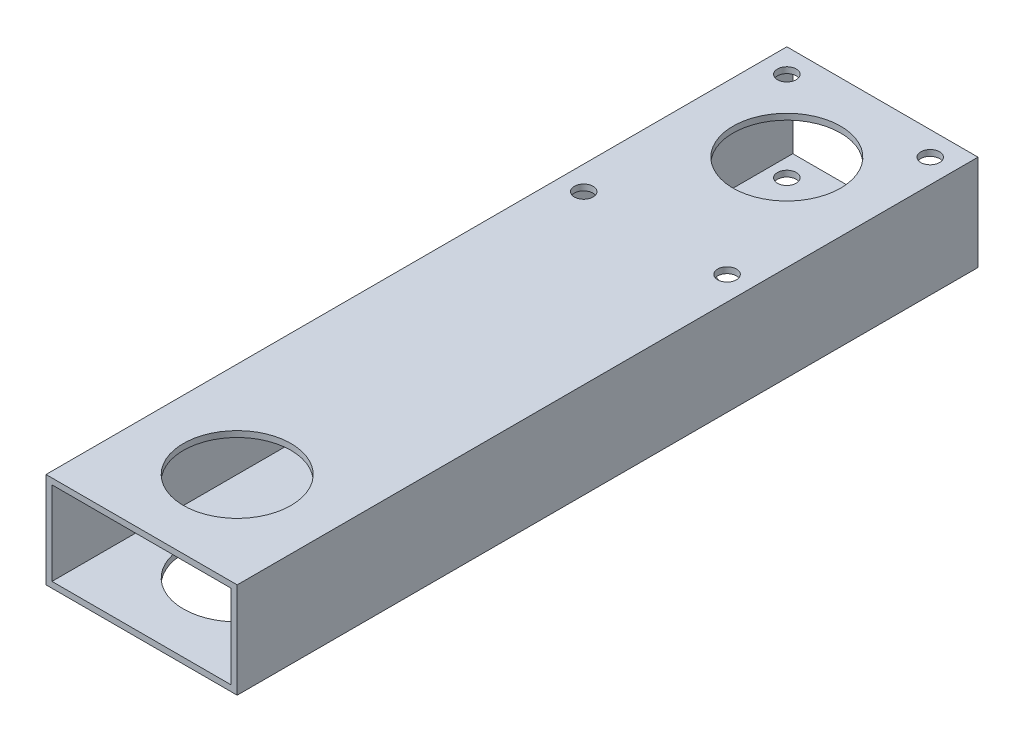
SolidWorks part; units mm, degrees
material "6061 Alloy"
ref_plane "Front Plane" through (0, 0, 0) normal (0, 0, 1) x (1, 0, 0)
ref_plane "Top Plane" through (0, 0, 0) normal (0, 1, 0) x (1, 0, 0)
ref_plane "Right Plane" through (0, 0, 0) normal (1, 0, 0) x (0, 0, -1)
sketch "Sketch1" plane through (0, 0, 0) normal (0, 0, 1) x (1, 0, 0)
  line L0 (-23.8125, 11.1125) -> (23.8125, 11.1125)
  line L2 (-25.4, 12.7) -> (25.4, 12.7)
  line L3 (-25.4, 12.7) -> (-25.4, -12.7)
  line L4 (-25.4, -12.7) -> (25.4, -12.7)
  line L5 (25.4, 12.7) -> (25.4, -12.7)
  line L10 (23.8125, 11.1125) -> (23.8125, -11.1125)
  line L11 (-23.8125, -11.1125) -> (23.8125, -11.1125)
  line L12 (-23.8125, 11.1125) -> (-23.8125, -11.1125)
  point P12 (0, 12.7)
  point P14 (25.4, 0)
  dimension "Wall Thickness" = 1.5875
  dimension "Outside Width" = 50.8
  dimension "Outside Height" = 25.4
  dimension "Inside Height" = 22.225
  dimension "Inside Width" = 47.625
sketch "Sketch2" plane through (0, 0, 0) normal (1, 0, 0) x (0, 0, -1)
  line L0 (98.425, 0) -> (-98.425, 0)
  point P4 (0, 0)
  point P7 (-98.425, 0)
  point P10 (98.425, 0)
  dimension "Length" = 196.85
sketch "Sketch3" plane through (0, 0, 0) normal (0, 0, 1) x (1, 0, 0)
  line L21 (25.4, 12.7) -> (-25.4, 12.7)
  line L22 (25.4, -12.7) -> (25.4, 12.7)
  line L23 (-25.4, -12.7) -> (25.4, -12.7)
  line L24 (-25.4, 12.7) -> (-25.4, -12.7)
  line L25 (25.4, 12.7) -> (-25.4, 12.7)
  line L26 (25.4, -12.7) -> (25.4, 12.7)
  line L27 (-25.4, -12.7) -> (25.4, -12.7)
  line L28 (-25.4, 12.7) -> (-25.4, -12.7)
  line L29 (23.8125, 11.1125) -> (-23.8125, 11.1125)
  line L30 (23.8125, -11.1125) -> (23.8125, 11.1125)
  line L31 (-23.8125, -11.1125) -> (23.8125, -11.1125)
  line L32 (-23.8125, 11.1125) -> (-23.8125, -11.1125)
  line L33 (23.8125, 11.1125) -> (-23.8125, 11.1125)
  line L34 (23.8125, -11.1125) -> (23.8125, 11.1125)
  line L35 (-23.8125, -11.1125) -> (23.8125, -11.1125)
  line L36 (-23.8125, 11.1125) -> (-23.8125, -11.1125)
  dimension "D1" = 0
  dimension "D2" = 0
extrude "Boss-Extrude1" add sketch "Sketch3" along normal up to vertex (98.425 mm away) and the other way up to vertex (98.425 mm away) up to point (0, 0, 98.425) other way up to point (0, 0, -98.425)
sketch "Drawing Reference" plane through (0, 0, 0) normal (1, 0, 0) x (0, 0, -1)
  line L0 (-98.425, 0) -> (98.425, 0) construction
  line L1 (0, -12.7) -> (0, 12.7) construction
  line L2 (-98.425, -12.7) -> (98.425, -12.7) construction
  line L5 (-98.425, 12.7) -> (98.425, 12.7) construction
  point P7 (-61.849, 0)
  point P8 (61.849, 0)
  dimension "D1" = 36.576
sketch "Sketch4" plane through (0, -12.7, 0) normal (0, -1, 0) x (1, 0, 0)
  line L0 (-25.4, 0) -> (0, 0) construction
  line L1 (-25.4, 98.425) -> (-25.4, -98.425) construction
  line L2 (0, 0) -> (0, -73.025) construction
  line L3 (0, 0) -> (0, 73.025) construction
  circle A0 centre (0, 73.025) radius 14.2875
  circle A1 centre (0, -73.025) radius 14.2875
extrude "Cut-Extrude3" cut sketch "Sketch4" against normal through all
hole_wizard "#10 Clearance Hole1" positions "Sketch5" profile "Sketch6" hole size "#10" standard "ANSI Inch" end condition through all
sketch "Sketch5" plane through (0, 12.7, 0) normal (0, 1, 0) x (1, 0, 0)
  point P0 (19.05, 38.1)
  point P3 (19.05, 92.075)
  point P6 (-19.05, 92.075)
  point P9 (-19.05, 38.1)
sketch "Sketch6" plane through (19.05, 12.7, -38.1) normal (1, 0, 0) x (0, 0, 1)
  line L0 (0, 0) -> (0, 25.4)
  line L1 (0, 25.4) -> (2.4892, 25.4)
  line L2 (2.4892, 25.4) -> (2.4892, 0)
  line L5 (2.4892, 0) -> (0, 0)
  line L11 (0, -6.35) -> (0, 107.95) construction
  dimension "Thru Hole Dia." = 4.9784
  dimension "Thru Hole Depth" = 25.4
sketch "Sketch7" plane through (0, -12.7, 0) normal (0, -1, 0) x (1, 0, 0)
  line L0 (-25.4, -31.75) -> (-342.9, -31.75) construction
  line L1 (-25.4, -31.75) -> (25.4, -31.75)
  line L2 (-25.4, 98.425) -> (-25.4, -98.425) construction
  line L3 (25.4, 98.425) -> (25.4, -98.425) construction
  line L4 (25.4, -31.75) -> (25.4, -98.425)
  line L5 (25.4, -98.425) -> (-25.4, -98.425)
  line L6 (-25.4, -98.425) -> (-25.4, -82.55)
  line L7 (-25.4, -82.55) -> (-342.9, -82.55) construction
  line L8 (-25.4, -82.55) -> (-104.2832, -82.55)
  line L9 (-104.2832, -82.55) -> (-104.2832, -31.75)
  line L10 (-104.2832, -31.75) -> (-25.4, -31.75)
  circle A0 centre (0, -73.2777) radius 14.5402
equation "\"D1@Drawing Reference\"=\"Outside Width@Sketch1\" * 0.72"
